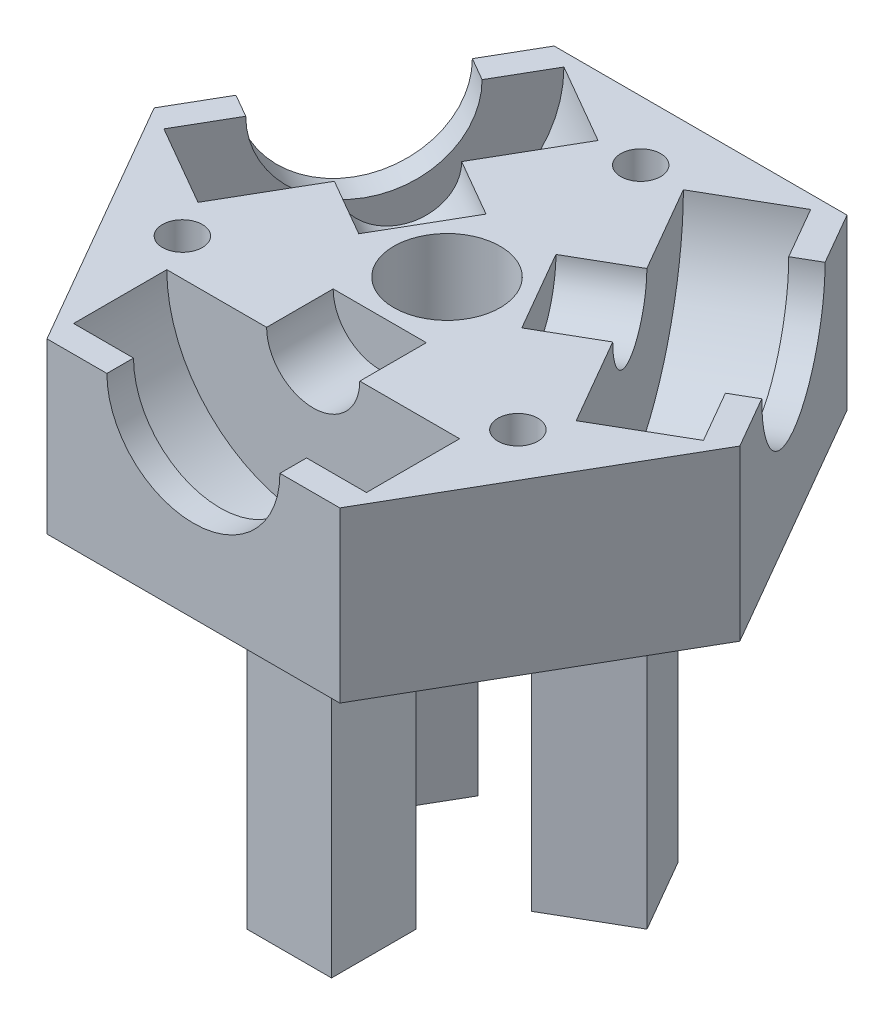
SolidWorks part; units mm, degrees
ref_plane "Front Plane" through (0, 0, 0) normal (0, 0, 1) x (1, 0, 0)
ref_plane "Top Plane" through (0, 0, 0) normal (0, 1, 0) x (1, 0, 0)
ref_plane "Right Plane" through (0, 0, 0) normal (1, 0, 0) x (0, 0, -1)
sketch "Sketch1" plane through (0, 0, 0) normal (0, 1, 0) x (1, 0, 0)
  line L1 (11, -19.0526) -> (22, 0)
  line L2 (22, 0) -> (11, 19.0526)
  line L3 (11, 19.0526) -> (-11, 19.0526)
  line L4 (-11, 19.0526) -> (-22, 0)
  line L5 (-22, 0) -> (-11, -19.0526)
  line L6 (-11, -19.0526) -> (11, -19.0526)
  circle A0 centre (0, 0) radius 19.0526 construction
  dimension "D1" = 22
extrude "Boss-Extrude1" add sketch "Sketch1" along normal blind 12.7 contours L4 L5 L6 L1 L2 L3
sketch "Sketch2" plane through (0, 0, 0) normal (0, -1, 0) x (1, 0, 0)
  circle A0 centre (0, 0) radius 4
  circle A1 centre (0, 0) radius 7
  dimension "D1" = 8
  dimension "D2" = 3
extrude "Boss-Extrude2" add sketch "Sketch2" along normal blind 3.5
sketch "Sketch4" plane through (0, 0, 0) normal (0, -1, 0) x (1, 0, 0)
  line L0 (11.8499, -3.1754) -> (6.3506, -0.0004)
  line L1 (-3.175, 11.85) -> (3.175, 11.85)
  line L2 (-3.175, 11.85) -> (-3.175, 5.5)
  line L3 (-3.175, 5.5) -> (3.175, 5.5)
  line L4 (3.175, 11.85) -> (3.175, 5.5)
  line L5 (-3.175, 11.85) -> (3.175, 5.5) construction
  line L6 (-3.175, 5.5) -> (3.175, 11.85) construction
  line L7 (11.8499, -3.1754) -> (8.6749, -8.6746)
  line L8 (8.6749, -8.6746) -> (3.1756, -5.4996)
  line L9 (6.3506, -0.0004) -> (3.1756, -5.4996)
  line L10 (-8.6749, -8.6746) -> (-3.1756, -5.4996)
  line L11 (-8.6749, -8.6746) -> (-11.8499, -3.1754)
  line L12 (-11.8499, -3.1754) -> (-6.3506, -0.0004)
  line L13 (-3.1756, -5.4996) -> (-6.3506, -0.0004)
  circle A1 centre (0, 0) radius 4 construction
  circle A2 centre (0, 0) radius 4 construction
  point P0 (0, 8.675)
  point P18 (0, 0)
  dimension "D1" = 6.35
  dimension "D2" = 1.5
  dimension "D4" = 1.5
  dimension "D5" = 1.5
  dimension "D3" = 3
extrude "Boss-Extrude4" add sketch "Sketch4" along normal blind 25.4
sketch "Sketch5" plane through (0, 12.7, 0) normal (0, 1, 0) x (1, 0, 0)
  line L14 (0, -19.0526) -> (0, -5.0526)
  line L15 (-11, -19.0526) -> (11, -19.0526) construction
  line L16 (0, -5.0526) -> (-3.5, -5.0526)
  line L17 (-3.5, -5.0526) -> (-3.5, -10.0526)
  line L18 (-3.5, -10.0526) -> (-11, -10.0526)
  line L19 (-11, -10.0526) -> (-11, -17.0526)
  line L20 (-11, -17.0526) -> (-6.5, -17.0526)
  line L21 (-6.5, -17.0526) -> (-6.5, -19.0526)
  line L22 (-6.5, -19.0526) -> (0, -19.0526)
  dimension "D1" = 6.5
  dimension "D2" = 11
  dimension "D3" = 2
  dimension "D4" = 7
  dimension "D5" = 5
  dimension "D6" = 3.5
revolve "Cut-Revolve1" cut sketch "Sketch5" angle 360 about L14
pattern_circular "CirPattern1" count 3 over 360 about axis through (0, -3.5, 0) along (0, 1, 0) of "Cut-Revolve1" reverse direction yes
sketch "Sketch6" plane through (0, 12.7, 0) normal (0, 1, 0) x (1, 0, 0)
  circle A0 centre (0, 0) radius 4
  dimension "D1" = 8
extrude "Cut-Extrude1" cut sketch "Sketch6" against normal through all
sketch "Sketch7" plane through (0, 12.7, 0) normal (0, 1, 0) x (1, 0, 0)
  line L0 (11, 19.0526) -> (-11, 19.0526) construction
  line L1 (-22, 0) -> (-11, -19.0526) construction
  line L2 (11, -19.0526) -> (22, 0) construction
  circle A0 centre (0, 14.5526) radius 1.5
  circle A1 centre (12.6029, -7.2763) radius 1.5
  circle A2 centre (-12.6029, -7.2763) radius 1.5
  point P11 (0, 0)
  dimension "D1" = 3
  dimension "D2" = 3
  dimension "D4" = 3
  dimension "D5" = 3
  dimension "D3" = 3
extrude "Cut-Extrude2" cut sketch "Sketch7" against normal up to surface (12.7 mm away) up to face at (0, 0, 0)
